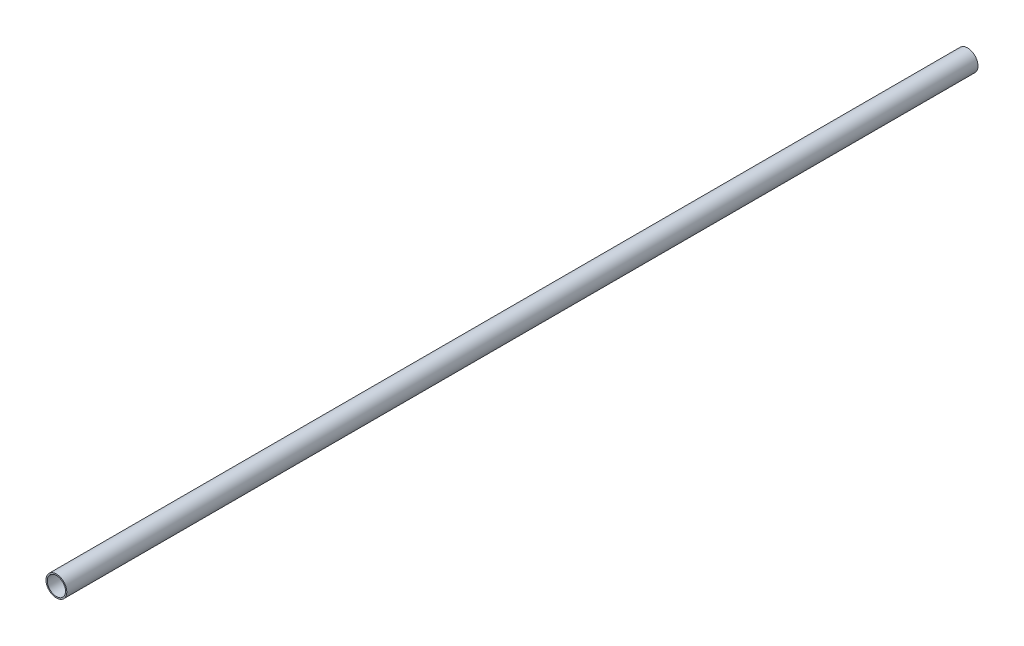
SolidWorks part; units mm, degrees
material "CarbonFiber"
ref_plane "Спереди" through (0, 0, 0) normal (0, 0, 1) x (1, 0, 0)
ref_plane "Сверху" through (0, 0, 0) normal (0, 1, 0) x (1, 0, 0)
ref_plane "Справа" through (0, 0, 0) normal (1, 0, 0) x (0, 0, -1)
sketch "Эскиз1" plane through (0, 0, 0) normal (0, 0, 1) x (1, 0, 0)
  circle A1 centre (0, 0) radius 8
  circle A2 centre (0, 0) radius 7
  dimension "D1" = 16
  dimension "D2" = 1
extrude "Бобышка-Вытянуть1" add sketch "Эскиз1" along normal mid plane 700
equation "\"D6@Fus\"=\"DMotor\"+1.2"
equation "\"D1@Fus\"=\"FusLenght\""
equation "\"D2@Fus\"=\"MotorArm\""
equation "\"D4@Fus\"=\"DFus\""
equation "\"D5@Fus\" = \"FusCentralPartLenght\""
equation "\"D4@FusCopy\" = \"FusTubeHeight\""
equation "\"D1@CentralPartCrossSection1\"=\"DFus\"*\"EllipseRatio\""
equation "\"D1@CentralPartCrossSection2\"=\"DFus\"*\"EllipseRatio\""
equation "\"D2@Frame\" = \"DFusTube\" + 1.2"
equation "\"DTailTube\"= 16mm'Диаметр трубки хвостового оперения"
equation "\"FusLenght\"= 700mm"
equation "\"DMotor\"= 35.2mm"
equation "\"MotorArm\"= 225mm"
equation "\"DFus\"= 140mm"
equation "\"DFusTube\"= 30mm'Диаметр трубки внутри фюзеляжа"
equation "\"FusTubeHeight\"= 40mm"
equation "\"FusCentralPartLenght\"= 350mm"
equation "\"FusNoseLenght\"= 170mm"
equation "\"WingOffset\"= 1mm'Расстояние от внутренней поверхности фюзеляжа до профиля крыла по вертикали"
equation "\"EllipseRatio\"= 0.95'Центральная часть фюзеляжа - эллипс. Этот параметр - отношение длин осей эллипса"
equation "\"FrameOffset\"= 0.6mm"
equation "\"DThreadedInsert\"= 3.6mm'Внешний диамер резьбовых втулок"
equation "\"CenterSectionLenght\"= 140mm'Длина центроплана"
equation "\"b\"= 1700mm'Размах"
equation "\"cwr\"= 236mm'Корневая хорда крыла"
equation "\"TR\"= 0.75'Сужение крыла"
equation "\"cwt\"= \"TR\" * \"cwr\"'Концевая хорда крыла"
equation "\"D3@Airfoil\"=\"cwr\""
equation "\"DWingMainSpar\"= 16mm'Диаметр главного лонжерона крыла"
equation "\"DWingSecondSpar\"= 8mm'Диаметр второго лонжерона крыла"
equation "\"WingSparsDistance\"= 80mm'Расстояния между отверстиями по лонжерон крыла"
equation "\"D7@Airfoil\"=\"DWingMainSpar\""
equation "\"D9@Airfoil\"=\"DWingSecondSpar\""
equation "\"D8@Airfoil\"=\"WingSparsDistance\"*2"
equation "\"c\"= 210mm'САХ крыла"
equation "\"FusTubeLenght\"= \"FusCentralPartLenght\" + \"FusNoseLenght\" + 10mm'Длина трубки фюзеляжа"
equation "\"bt\"=291mm'Высота лопатки хвоста"
equation "\"D1@Эскиз1\"=\"DTailTube\""
equation "\"TailTubeLenght\"=700mm'Длина хвостовой балки"
equation "\"D1@Бобышка-Вытянуть1\"=\"TailTubeLenght\""
